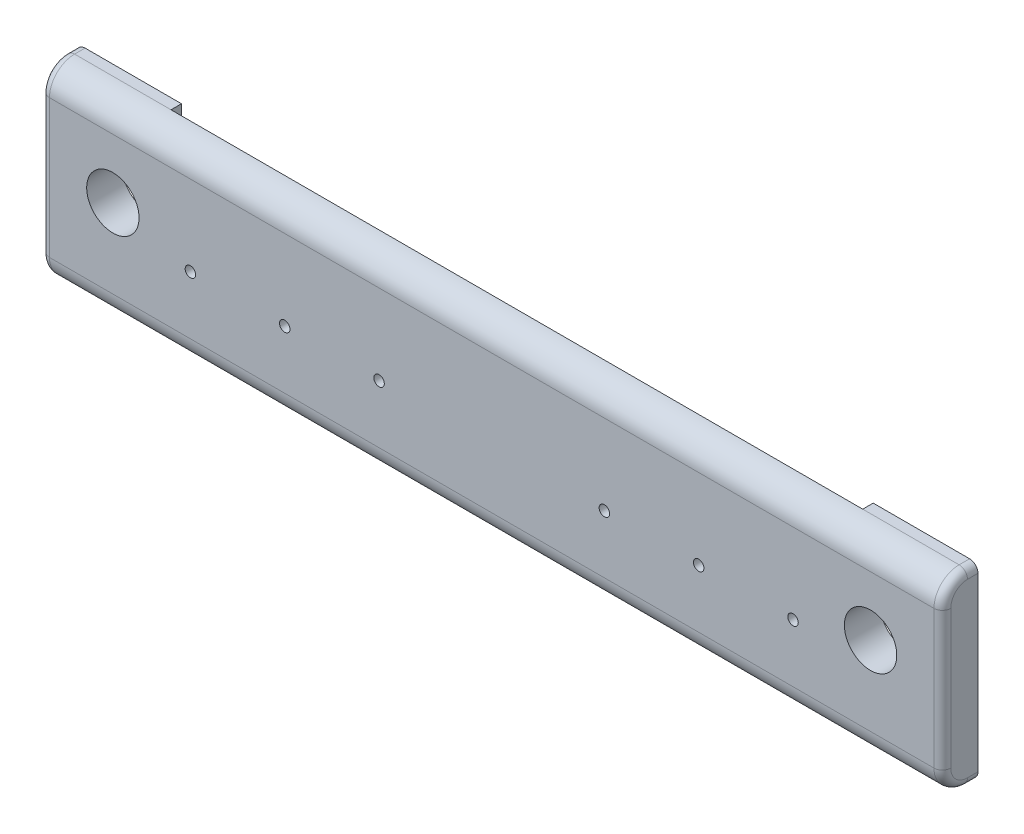
SolidWorks part; units mm, degrees
ref_plane "Plano frontal" through (0, 0, 0) normal (0, 0, 1) x (1, 0, 0)
ref_plane "Plano superior" through (0, 0, 0) normal (0, 1, 0) x (1, 0, 0)
ref_plane "Plano direito" through (0, 0, 0) normal (1, 0, 0) x (0, 0, -1)
sketch "Esboço1" plane through (0, 0, 0) normal (0, 0, 1) x (1, 0, 0)
  line L1 (-21.5, -4.5) -> (21.5, -4.5)
  line L2 (-21.5, -4.5) -> (-21.5, 4.5)
  line L3 (-21.5, 4.5) -> (21.5, 4.5)
  line L4 (21.5, -4.5) -> (21.5, 4.5)
  line L5 (-21.5, -4.5) -> (21.5, 4.5) construction
  line L6 (-21.5, 4.5) -> (21.5, -4.5) construction
  point P0 (0, 0)
  dimension "D1" = 43
  dimension "D2" = 9
extrude "Ressalto-extrusão1" add sketch "Esboço1" along normal blind 1.2
sketch "Esboço4" plane through (0, 0, 0) normal (0, 0, -1) x (-1, 0, 0)
  line L0 (21.5, -4.5) -> (-21.5, -4.5) construction
  line L1 (21.5, 4.5) -> (16.5, 4.5)
  line L2 (21.5, 4.5) -> (21.5, -4.5)
  line L3 (21.5, -4.5) -> (16.5, -4.5)
  line L4 (16.5, 4.5) -> (16.5, -4.5)
  line L6 (-21.5, 4.5) -> (-16.5, 4.5)
  line L7 (-21.5, 4.5) -> (-21.5, -4.5)
  line L8 (-21.5, -4.5) -> (-16.5, -4.5)
  line L9 (-16.5, 4.5) -> (-16.5, -4.5)
  dimension "D1" = 5
  dimension "D2" = 5
extrude "Ressalto-extrusão4" add sketch "Esboço4" along normal blind 0.5
fillet "Filete1" radius 1.2 1 edges at (0, 4.5, 1.2)
fillet "Filete2" radius 1.2 1 edges at (0, -4.5, 1.2)
sketch "Esboço6" plane through (0, 0, -0.5) normal (0, 0, -1) x (-1, 0, 0)
  line L0 (-19, 0) -> (-19, -4.5) construction
  line L1 (-21.5, -4.5) -> (-16.5, -4.5) construction
  line L2 (-18.075, 0.4702) -> (18.075, 0.4702) construction
  line L3 (-21.5, -3.3) -> (-21.5, 3.3) construction
  circle A0 centre (-18.075, 0.4702) radius 1.25
  circle A1 centre (18.075, 0.4702) radius 1.25
  dimension "D1" = 2.5
  dimension "D4" = 2.5
  dimension "D2" = 36.15
  dimension "D3" = 3.425
extrude "Corte-extrusão2" cut sketch "Esboço6" against normal blind 5.5
fillet "Filete3" radius 0.4 5 edges at (-21.5, -4.5, -0.25) (-21.5, 4.5, -0.25) (-21.5, 4.1485, 0.8485) (-21.5, 0, 1.2) (-21.5, -4.1485, 0.8485)
fillet "Filete4" radius 0.4 5 edges at (21.5, -4.5, -0.25) (21.5, -4.1485, 0.8485) (21.5, 4.5, -0.25) (21.5, 4.1485, 0.8485) (21.5, 0, 1.2)
sketch "Esboço7" plane through (0, 0, 1.2) normal (0, 0, 1) x (1, 0, 0)
  line L0 (-18.075, 0.0702) -> (-18.075, -0.5298) construction
  line L1 (-18.075, -0.5298) -> (7.325, -0.5298) construction
  line L2 (18.075, 0.4702) -> (18.075, -0.1298) construction
  line L3 (3.0985, -0.5298) -> (21.9876, -0.5298) construction
  circle A0 centre (14.375, -0.5298) radius 0.25
  circle A1 centre (-14.375, -0.5298) radius 0.25
  circle A2 centre (-9.875, -0.5298) radius 0.25
  circle A3 centre (-5.375, -0.5298) radius 0.25
  circle A4 centre (9.875, -0.5298) radius 0.25
  circle A5 centre (5.375, -0.5298) radius 0.25
  point P22 (8.7107, -2.0642)
  dimension "D3" = 0.5
  dimension "D6" = 0.5
  dimension "D7" = 0.5
  dimension "D9" = 0.5
  dimension "D10" = 0.5
  dimension "D11" = 0.5
  dimension "D12" = 3.7
  dimension "D1" = 0.6
  dimension "D2" = 3.7
  dimension "D4" = 4.5
  dimension "D5" = 4.5
  dimension "D8" = 0.6
  dimension "D13" = 4.5
  dimension "D14" = 4.5
extrude "Corte-extrusão3" cut sketch "Esboço7" against normal through all
